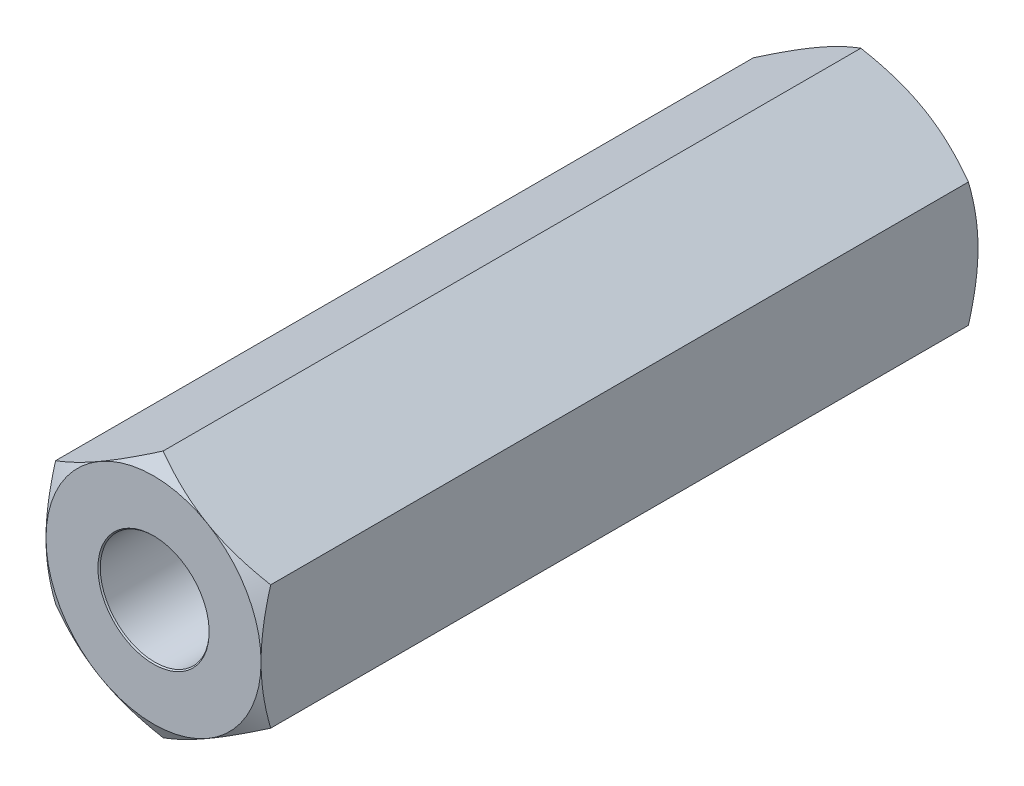
SolidWorks part; units mm, degrees
material "2011 Alloy"
ref_plane "Front Plane" through (0, 0, 0) normal (0, 0, 1) x (1, 0, 0)
ref_plane "Top Plane" through (0, 0, 0) normal (0, 1, 0) x (1, 0, 0)
ref_plane "Right Plane" through (0, 0, 0) normal (1, 0, 0) x (0, 0, -1)
sketch "Sketch3" plane through (0, 0, 0) normal (1, 0, 0) x (0, 0, -1)
  line L0 (-15.875, 0) -> (15.875, 0) construction
  line L1 (0, 4.7625) -> (0, -4.7625) construction
  line L2 (-15.875, 2.413) -> (-15.875, -2.413) construction
  point P2 (3.175, 0)
  point P3 (-3.175, 0)
  dimension "Length" = 31.75
  dimension "Min Thread Length" = 12.7
  dimension "D1" = 12.7
  dimension "Thread Dia" = 4.826
  dimension "Hex" = 9.525
sketch "Sketch1" plane through (0, 0, 0) normal (0, 0, 1) x (1, 0, 0)
  line L1 (0, 5.4993) -> (-4.7625, 2.7496)
  line L2 (-4.7625, 2.7496) -> (-4.7625, -2.7496)
  line L3 (-4.7625, -2.7496) -> (0, -5.4993)
  line L4 (0, -5.4993) -> (4.7625, -2.7496)
  line L5 (4.7625, -2.7496) -> (4.7625, 2.7496)
  line L6 (4.7625, 2.7496) -> (0, 5.4993)
  circle A0 centre (0, 0) radius 4.7625 construction
  circle A1 centre (0, 0) radius 2.413
extrude "Extrude1" add sketch "Sketch1" along normal up to vertex (15.875 mm away) and the other way up to vertex (15.875 mm away) up to point (0, 0, 15.875) other way up to point (0, 0, -15.875)
sketch "Sketch11" plane through (0, 0, -15.875) normal (0, 0, -1) x (-1, 0, 0)
  circle A0 centre (0, 0) radius 2.413 construction
  circle A1 centre (0, 0) radius 2.413
curve "Helix/Spiral1" pitch 0.7937 height 32.5437 turns 41 parameters "Pitch"=0.7937
sketch "Sketch12" plane through (0, 0, 0) normal (1, 0, 0) x (0, 0, -1)
  line L0 (16.5695, 2.413) -> (15.875, 2.413)
  line L1 (16.5695, 2.413) -> (16.2719, 1.8974)
  line L2 (16.2719, 1.8974) -> (16.1727, 1.8974)
  line L3 (16.1727, 1.8974) -> (15.875, 2.413)
  line L4 (16.2223, 1.8974) -> (16.2223, 2.413) construction
  line L5 (16.4207, 2.1552) -> (16.0238, 2.1552) construction
  dimension "D1" = 0.0992
  dimension "D2" = 0.3969
  dimension "D3" = 60
sweep "Sweep1" [suppressed] add profiles "Sketch12" path "Helix/Spiral1"
sketch "Sketch6" plane through (0, 0, -15.875) normal (0, 0, -1) x (-1, 0, 0)
  line L6 (0, 5.4993) -> (-4.7625, 2.7496)
  line L7 (-4.7625, 2.7496) -> (-4.7625, -2.7496)
  line L8 (-4.7625, -2.7496) -> (0, -5.4993)
  line L9 (0, -5.4993) -> (4.7625, -2.7496)
  line L10 (4.7625, -2.7496) -> (4.7625, 2.7496)
  line L11 (4.7625, 2.7496) -> (0, 5.4993)
  line L12 (0, 5.4993) -> (-4.7625, 2.7496)
  line L13 (-4.7625, 2.7496) -> (-4.7625, -2.7496)
  line L14 (-4.7625, -2.7496) -> (0, -5.4993)
  line L15 (0, -5.4993) -> (4.7625, -2.7496)
  line L16 (4.7625, -2.7496) -> (4.7625, 2.7496)
  line L17 (4.7625, 2.7496) -> (0, 5.4993)
  dimension "D1" = 0
extrude "Extrude2" [suppressed] cut sketch "Sketch6" along normal through all
sketch "Sketch7" plane through (0, 0, -15.875) normal (0, 0, -1) x (-1, 0, 0)
  circle A2 centre (0, 0) radius 2.4638
  circle A3 centre (0, 0) radius 2.4638
  dimension "D1" = 0.0508
extrude "Extrude3" cut sketch "Sketch7" against normal through all draft 43
sketch "Sketch8" plane through (0, 0, -15.875) normal (0, 0, -1) x (-1, 0, 0)
  circle A0 centre (0, 0) radius 4.7625 construction
  circle A1 centre (0, 0) radius 4.7625
extrude "Extrude4" cut sketch "Sketch8" against normal through all draft 60 flip side to cut
mirror "Mirror1" about plane through (0, 0, 0) normal (0, 0, 1) of "Extrude2", "Extrude3", "Extrude4"
sketch "Sketch9" [suppressed] plane through (0, 0, 0) normal (1, 0, 0) x (0, 0, -1)
  line L1 (-3.175, 2.4638) -> (3.175, 2.4638)
  line L2 (-3.175, 2.4638) -> (-3.175, 0)
  line L3 (-3.175, 0) -> (3.175, 0)
  line L4 (3.175, 2.4638) -> (3.175, 0)
  line L7 (-15.875, 0) -> (15.875, 0) construction
revolve "Revolve" [suppressed] add sketch "Sketch9" angle 360 about L0
sketch "Sketch10" [suppressed] plane through (0, 0, 0) normal (1, 0, 0) x (0, 0, -1)
  line L0 (15.875, 2.413) -> (3.175, 2.413)
  line L1 (-15.875, 2.413) -> (-3.175, 2.413)
  line L2 (3.175, 2.413) -> (3.175, -2.413)
  line L3 (-15.875, -2.4638) -> (-3.175, -2.4638)
  line L4 (-3.175, 2.413) -> (-3.175, -2.4638)
  line L5 (3.175, -2.413) -> (15.875, -2.413)
equation "\"D1@Sketch3\" = \"Min Thread Length@Sketch3\""
equation "\"D3@Helix/Spiral1\" = \"Length@Sketch3\"+\"Pitch@Helix/Spiral1\""
equation "\"D1@Sketch12\" = \"Pitch@Helix/Spiral1\"*.125"
equation "\"D2@Sketch12\" = \"Pitch@Helix/Spiral1\"*.5"
